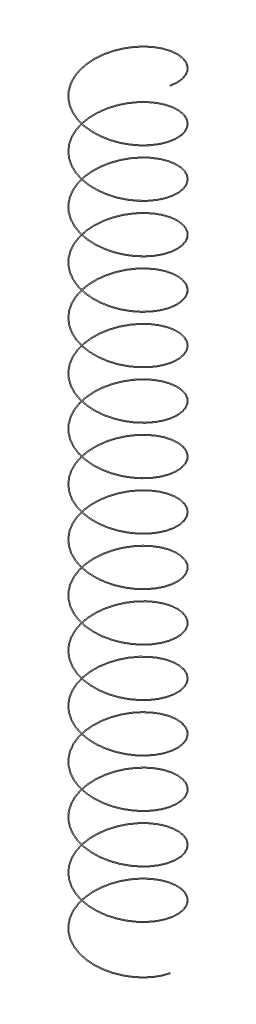
SolidWorks part; units mm, degrees
note: '?' marks a value the reader was unsure of.
ref_plane "Front Plane" through (0, 0, 0) normal (0, 0, 1) x (1, 0, 0)
ref_plane "Top Plane" through (0, 0, 0) normal (0, 1, 0) x (1, 0, 0)
ref_plane "Right Plane" through (0, 0, 0) normal (1, 0, 0) x (0, 0, -1)
sketch "Sketch1" plane through (0, 0, 0) normal (0, 1, 0) x (1, 0, 0)
  circle A0 centre (0, 0) radius 27.5
  dimension "D1" = 55
curve "Helix/Spiral1" pitch 31.3 height 500.8 turns 16
sketch "Sketch2" plane through (0, 0, 0) normal (0, 0, 1) x (1, 0, 0)
  circle A0 centre (27.5, 0) radius 0.25
  dimension "D1" = 0.5
sweep "Sweep1" add profiles "Sketch2" path "Helix/Spiral1"
ref_axis "Axis1" through (0, 0, 0) along (0, 1, 0)?
